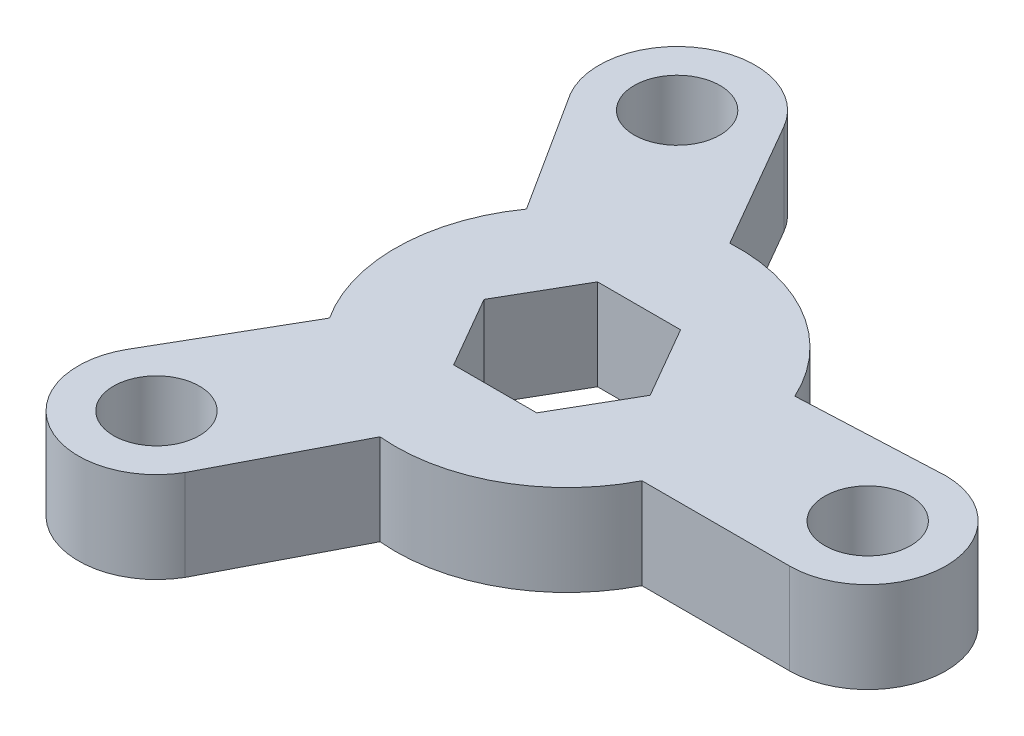
SolidWorks part; units mm, degrees
ref_plane "Front" through (0, 0, 0) normal (0, 0, 1) x (1, 0, 0)
ref_plane "Top" through (0, 0, 0) normal (0, 1, 0) x (1, 0, 0)
ref_plane "Right" through (0, 0, 0) normal (1, 0, 0) x (0, 0, -1)
sketch "Sketch1" plane through (0, 0, 0) normal (0, 1, 0) x (1, 0, 0)
  line L0 (2.5148, 0.2447) -> (13.0148, 0.2447)
  line L1 (2.5148, 0.2447) -> (-2.7352, 9.338)
  line L2 (2.5148, 0.2447) -> (-2.7352, -8.8486)
  line L3 (2.5148, 0.2447) -> (-2.7352, 9.338) construction
  line L10 (2.5148, 0.2447) -> (13.0148, 0.2447) construction
  line L11 (13.0148, -2.4841) -> (7.8583, -2.4841)
  line L12 (13.0148, 2.9736) -> (7.9691, 2.7447)
  line L13 (-5.0985, -7.4841) -> (-2.5203, -3.0185)
  line L14 (-0.372, -10.213) -> (1.9526, -5.7289)
  line L15 (-0.372, 10.7024) -> (2.2062, 6.2368)
  line L16 (-5.0985, 7.9736) -> (-2.3775, 3.7183)
  line L18 (1.0642, -2.2678) -> (3.9654, -2.2678)
  line L19 (3.9654, -2.2678) -> (5.4159, 0.2447)
  line L20 (5.4159, 0.2447) -> (3.9654, 2.7572)
  line L21 (3.9654, 2.7572) -> (1.0642, 2.7572)
  line L22 (1.0642, 2.7572) -> (-0.3864, 0.2447)
  line L23 (-0.3864, 0.2447) -> (1.0642, -2.2678)
  circle A0 centre (-2.7352, 9.338) radius 1.5
  circle A1 centre (13.0148, 0.2447) radius 1.5
  circle A2 centre (-2.7352, -8.8486) radius 1.5
  circle A3 centre (2.5148, 0.2447) radius 2.5125 construction
  arc A4 (-0.372, 10.7024) -> (-5.0985, 7.9736) centre (-2.7352, 9.338) ccw
  circle A5 centre (2.5148, 0.2447) radius 6
  arc A6 (13.0148, -2.4841) -> (13.0148, 2.9736) centre (13.0148, 0.2447) ccw
  arc A7 (-5.0985, -7.4841) -> (-0.372, -10.213) centre (-2.7352, -8.8486) ccw
  point P39 (2.5148, 0.2447)
  dimension "D1" = 3
  dimension "D2" = 120
  dimension "D3" = 3
extrude "Boss-Extrude1" add sketch "Sketch1" along normal blind 3.175 contours L11 A6 L12 A5 A1 | A5 L0 L21 L2 | L0 A5 L1 L18 | L1 A5 L2 L20 L19 | L13 A7 L14 A5 A2 | A5 L15 A4 L16 A0 region at (4.3914, 0, -3.4951) region at (4.3914, 0, 3.0056) region at (-1.2384, 0, -0.2447) region at (11.4967, 0, -0.1921) region at (-1.9307, 0, -8.0496) region at (-2.0217, 0, 7.5076)
